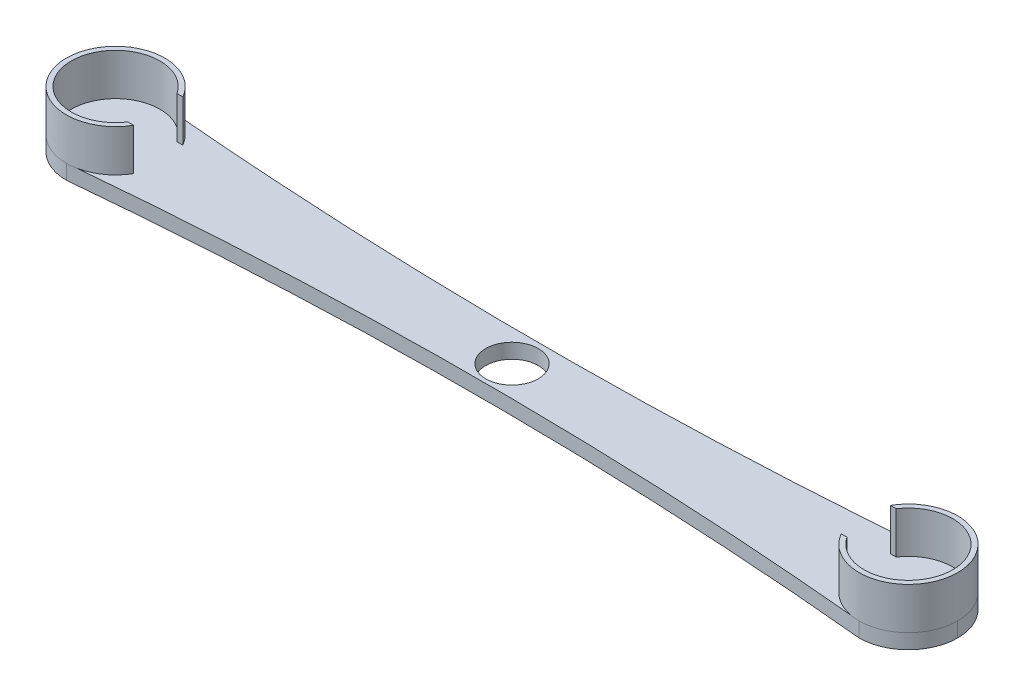
SolidWorks part; units mm, degrees
material "PET"
ref_plane "Front Plane" through (0, 0, 0) normal (0, 0, 1) x (1, 0, 0)
ref_plane "Top Plane" through (0, 0, 0) normal (0, 1, 0) x (1, 0, 0)
ref_plane "Right Plane" through (0, 0, 0) normal (1, 0, 0) x (0, 0, -1)
sketch "Sketch1" plane through (0, 0, 0) normal (0, 1, 0) x (1, 0, 0)
  line L5 (90.5, -10) -> (5.3022, -0.5859) construction
  line L6 (90.5, 10) -> (5.3022, 0.5859) construction
  line L10 (-90.5, -10) -> (-90.5, 10)
  line L11 (90.5, 10) -> (80.5, 10)
  line L13 (90.5, -10) -> (80.5, -10)
  line L15 (-90.5, -10) -> (-80.5, -10)
  line L17 (-90.5, 10) -> (-80.5, 10)
  line L19 (90.5, 10) -> (90.5, -10)
  line L20 (-80.5, 10) -> (0, 2.75) construction
  line L21 (0, 2.75) -> (80.5, 10) construction
  line L22 (-80.5, -10) -> (0, -2.265) construction
  line L23 (0, -2.265) -> (80.5, -10) construction
  line L24 (-5.3022, -0.5859) -> (-90.5, -10) construction
  line L25 (5.3022, -0.5859) -> (-90.5, 10) construction
  circle A0 centre (0, 0) radius 5.3345
  spline S0 degree 2 poles (-80.5, 10) (0, 2.75) (80.5, 10) knots 0 0 0 1 1 1
  spline S1 degree 2 poles (-80.5, -10) (0, -2.265) (80.5, -10) knots 0 0 0 1 1 1
  point P0 (0, 0)
  point P18 (0, 0)
  point P19 (0, -2.265)
  point P20 (0, 0)
  point P21 (0, 0)
  point P22 (0, 0)
  point P23 (0, 0)
  point P24 (0, 0)
extrude "Boss-Extrude1" add sketch "Sketch1" along normal blind 3
sketch "Sketch3" plane through (0, 3, 0) normal (0, 1, 0) x (1, 0, 0)
  line L1 (71.8397, 5) -> (73.0167, 5)
  line L9 (71.8397, -5) -> (73.0167, -5)
  line L12 (-73.0167, -5) -> (-71.8397, -5)
  line L14 (-73.0167, 5) -> (-71.8397, 5)
  arc A0 (73.0167, -5) -> (73.0167, 5) centre (80.5, 0) ccw
  arc A1 (71.8397, -5) -> (71.8397, 5) centre (80.5, 0) ccw
  arc A2 (-73.0167, 5) -> (-73.0167, -5) centre (-80.5, 0) ccw
  arc A3 (-71.8397, 5) -> (-71.8397, -5) centre (-80.5, 0) ccw
  point P10 (0, 0)
  point P16 (0, 0)
extrude "Boss-Extrude3" add sketch "Sketch3" along normal blind 8.5
fillet "Fillet1" radius 10 4 edges at (-90.5, 1.5, 10) (-90.5, 1.5, -10) (90.5, 1.5, -10) (90.5, 1.5, 10)
